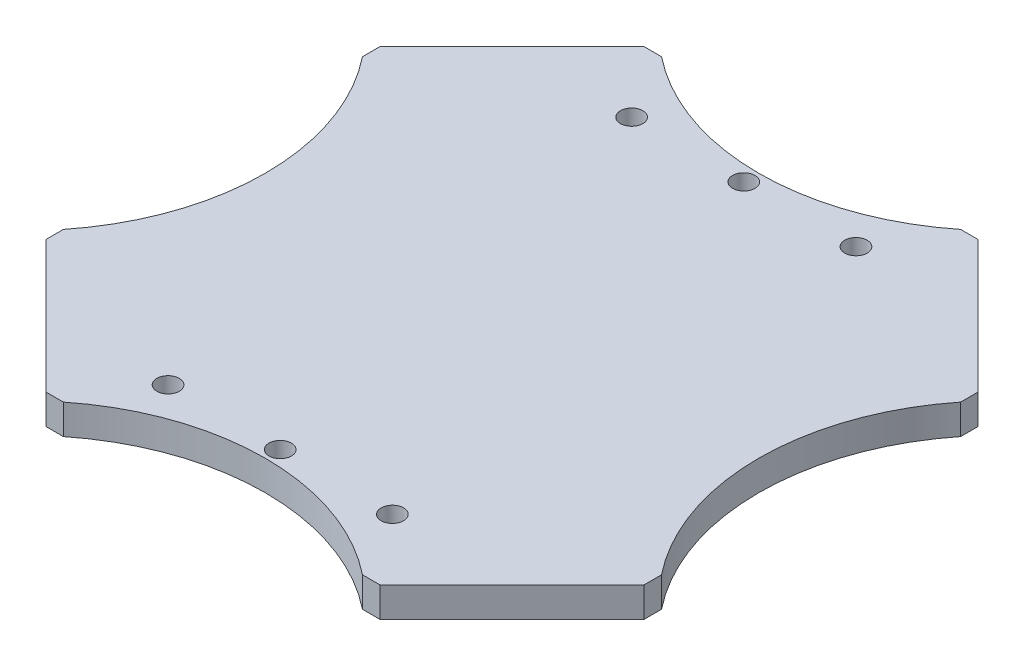
SolidWorks part; units mm, degrees
ref_plane "Front Plane" through (0, 0, 0) normal (0, 0, 1) x (1, 0, 0)
ref_plane "Top Plane" through (0, 0, 0) normal (0, 1, 0) x (1, 0, 0)
ref_plane "Right Plane" through (0, 0, 0) normal (1, 0, 0) x (0, 0, -1)
sketch "Sketch1" plane through (0, 0, 0) normal (0, 1, 0) x (1, 0, 0)
  line L0 (22.3223, 40) -> (-22.3223, 40)
  line L1 (-22.3223, 40) -> (-40, 22.3223)
  line L2 (-40, 22.3223) -> (-40, -22.3223)
  line L3 (-40, -22.3223) -> (-22.3223, -40)
  line L4 (-22.3223, -40) -> (22.3223, -40)
  line L5 (22.3223, -40) -> (40, -22.3223)
  line L6 (40, -22.3223) -> (40, 22.3223)
  line L7 (40, 22.3223) -> (22.3223, 40)
  dimension "D1" = 80
  dimension "D2" = 80
  dimension "D3" = 40
  dimension "D4" = 40
  dimension "D5" = 25
  dimension "D6" = 25
  dimension "D7" = 25
  dimension "D8" = 25
  dimension "D9" = 135
  dimension "D10" = 135
  dimension "D11" = 135
  dimension "D12" = 135
extrude "Boss-Extrude1" add sketch "Sketch1" along normal blind 4
sketch "Sketch2" plane through (0, 4, 0) normal (0, 1, 0) x (1, 0, 0)
  line L0 (-40, 22.3223) -> (-40, -22.3223) construction
  line L1 (-40, 20) -> (-40, -20)
  line L5 (20, 40) -> (-20, 40)
  line L6 (40, -20) -> (40, 20)
  line L7 (-20, -40) -> (20, -40)
  arc A0 (-40, 20) -> (-40, -20) centre (-65.0714, 0) cw
  arc A4 (20, 40) -> (-20, 40) centre (0, 65.0714) cw
  arc A5 (40, -20) -> (40, 20) centre (65.0714, 0) cw
  arc A6 (-20, -40) -> (20, -40) centre (0, -65.0714) cw
  point P18 (0, 0)
  dimension "D1" = 7
  dimension "D2" = 40
extrude "Cut-Extrude1" cut sketch "Sketch2" against normal through all
sketch "Sketch5" plane through (0, 0, 0) normal (0, -1, 0) x (1, 0, 0)
  line L0 (2.2, 0) -> (-2.2, 0) construction
  circle A0 centre (-15, 31) radius 1.5
  circle A1 centre (0, 31) radius 1.5
  circle A2 centre (15, 31) radius 1.5
  circle A3 centre (15, -31) radius 1.5
  circle A4 centre (0, -31) radius 1.5
  circle A5 centre (-15, -31) radius 1.5
  point P8 (-2.3585, 4.0202)
  point P10 (-0.3135, 20.879)
  dimension "D1" = 3
  dimension "D2" = 3
  dimension "D3" = 3
  dimension "D4" = 15
  dimension "D5" = 15
  dimension "D6" = 31
  dimension "D7" = 0
extrude "Cut-Extrude2" cut sketch "Sketch5" against normal through all
